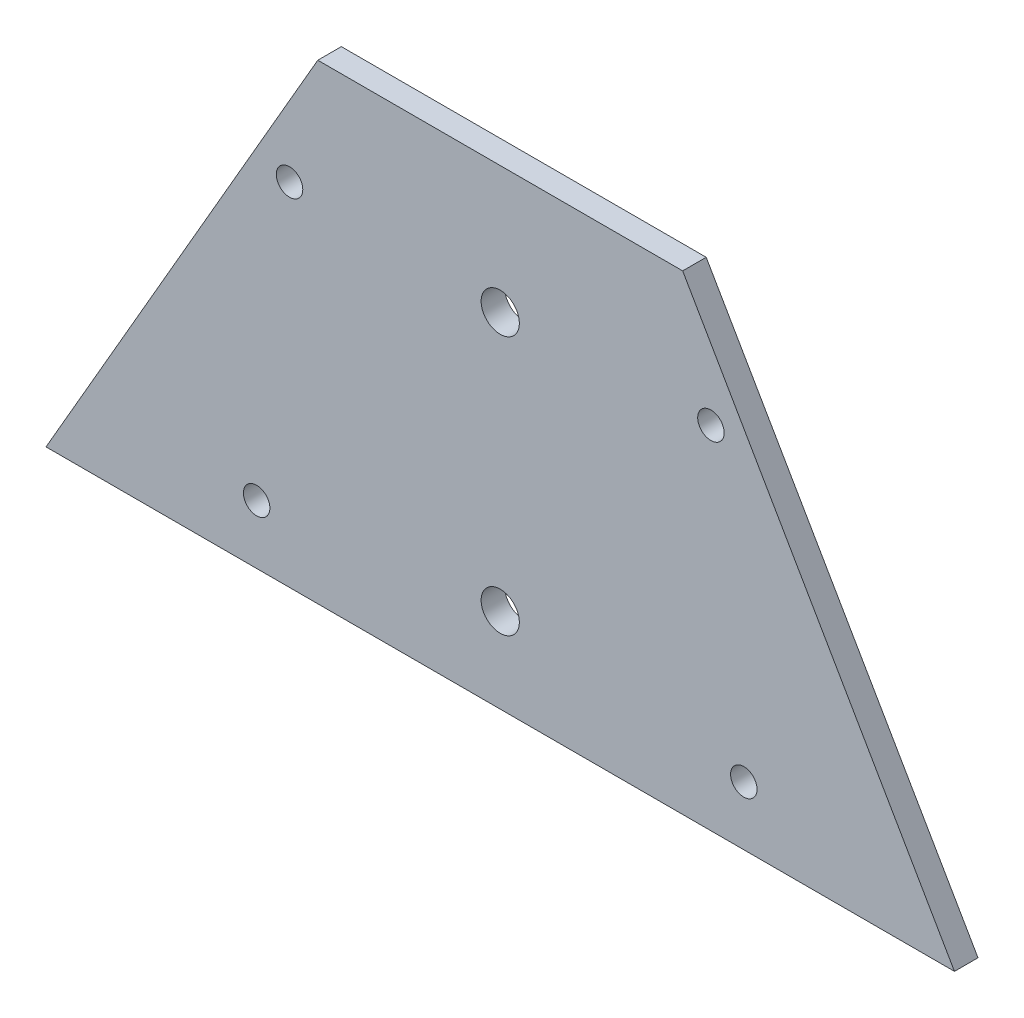
SolidWorks part; units mm, degrees
material "6061-T6 (SS)"
ref_plane "Front" through (0, 0, 0) normal (0, 0, 1) x (1, 0, 0)
ref_plane "Top" through (0, 0, 0) normal (0, 1, 0) x (1, 0, 0)
ref_plane "Right" through (0, 0, 0) normal (1, 0, 0) x (0, 0, -1)
sketch "Sketch1" plane through (0, 0, 0) normal (0, 0, 1) x (1, 0, 0)
  line L0 (-49.2125, 113.0795) -> (49.2125, 113.0795)
  line L1 (-122.536, -13.9205) -> (0, 0) construction
  line L2 (-49.2125, 113.0795) -> (0, 0) construction
  line L3 (49.2125, 113.0795) -> (122.536, -13.9205)
  line L4 (122.536, -13.9205) -> (-122.536, -13.9205)
  line L5 (122.536, -13.9205) -> (73.3235, -99.159) construction
  line L6 (73.3235, -99.159) -> (-73.3235, -99.159) construction
  line L7 (-73.3235, -99.159) -> (-122.536, -13.9205) construction
  line L8 (-122.536, -13.9205) -> (-49.2125, 113.0795)
  line L9 (0, 0) -> (49.2125, 113.0795) construction
  line L10 (0, 0) -> (122.536, -13.9205) construction
  line L11 (0, 0) -> (73.3235, -99.159) construction
  line L13 (0, 0) -> (-73.3235, -99.159) construction
  dimension "D1" = 98.425
  dimension "D2" = 127
extrude "Boss-Extrude1" add sketch "Sketch1" along normal blind 6.35
ref_axis "Axis1" through (0, 0, 0) along (0, 0, 1)
sketch "Sketch2" plane through (0, 0, 6.35) normal (0, 0, 1) x (1, 0, 0)
  line L0 (0, 0) -> (0, 78.8054) construction
  line L1 (0, 0) -> (0, 8.9554) construction
  line L3 (49.2125, 113.0795) -> (-49.2125, 113.0795) construction
  line L4 (56.8386, 80.8207) -> (93.2066, 17.8295) construction
  line L5 (93.2066, 17.8295) -> (65.7103, 1.9545) construction
  line L6 (65.7103, 1.9545) -> (29.3423, 64.9457) construction
  line L7 (29.3423, 64.9457) -> (56.8386, 80.8207) construction
  line L9 (122.536, -13.9205) -> (49.2125, 113.0795) construction
  line L10 (-122.536, -13.9205) -> (122.536, -13.9205) construction
  point P12 (122.536, -13.9205)
  dimension "D1" = 69.85
  dimension "D2" = 34.2741
  dimension "D3" = 9.525
  dimension "D4" = 31.75
  dimension "D5" = 31.75
  dimension "D6" = 15.875
hole_wizard "3/8 Clearance Hole1" positions "Sketch4" profile "Sketch3" hole size "3/8" standard "ANSI Inch" end condition through all
sketch "Sketch4" plane through (0, 0, 6.35) normal (0, 0, 1) x (1, 0, 0)
  point P0 (0, 78.8054)
  point P3 (0, 8.9554)
sketch "Sketch3" plane through (0, 78.8054, 6.35) normal (1, 0, 0) x (0, -1, 0)
  line L0 (0, 0) -> (0, 6.35)
  line L1 (0, 6.35) -> (5.1587, 6.35)
  line L2 (5.1587, 6.35) -> (5.1587, 0)
  line L5 (5.1587, 0) -> (0, 0)
  line L11 (0, -6.35) -> (0, 107.95) construction
  dimension "Thru Hole Dia." = 10.3175
  dimension "Thru Hole Depth" = 6.35
hole_wizard "1/4 Clearance Hole1" positions "Sketch6" profile "Sketch5" hole size "1/4" standard "ANSI Inch" end condition through all
sketch "Sketch6" plane through (0, 0, 6.35) normal (0, 0, 1) x (1, 0, 0)
  point P9 (65.7103, 1.9545)
  point P16 (56.8386, 80.8207)
sketch "Sketch5" plane through (65.7103, 1.9545, 6.35) normal (1, 0, 0) x (0, -1, 0)
  line L0 (0, 0) -> (0, 6.35)
  line L1 (0, 6.35) -> (3.5712, 6.35)
  line L2 (3.5712, 6.35) -> (3.5712, 0)
  line L5 (3.5712, 0) -> (0, 0)
  line L11 (0, -6.35) -> (0, 107.95) construction
  dimension "Thru Hole Dia." = 7.1425
  dimension "Thru Hole Depth" = 6.35
mirror "Mirror1" about plane through (0, 0, 0) normal (1, 0, 0) of "1/4 Clearance Hole1"
